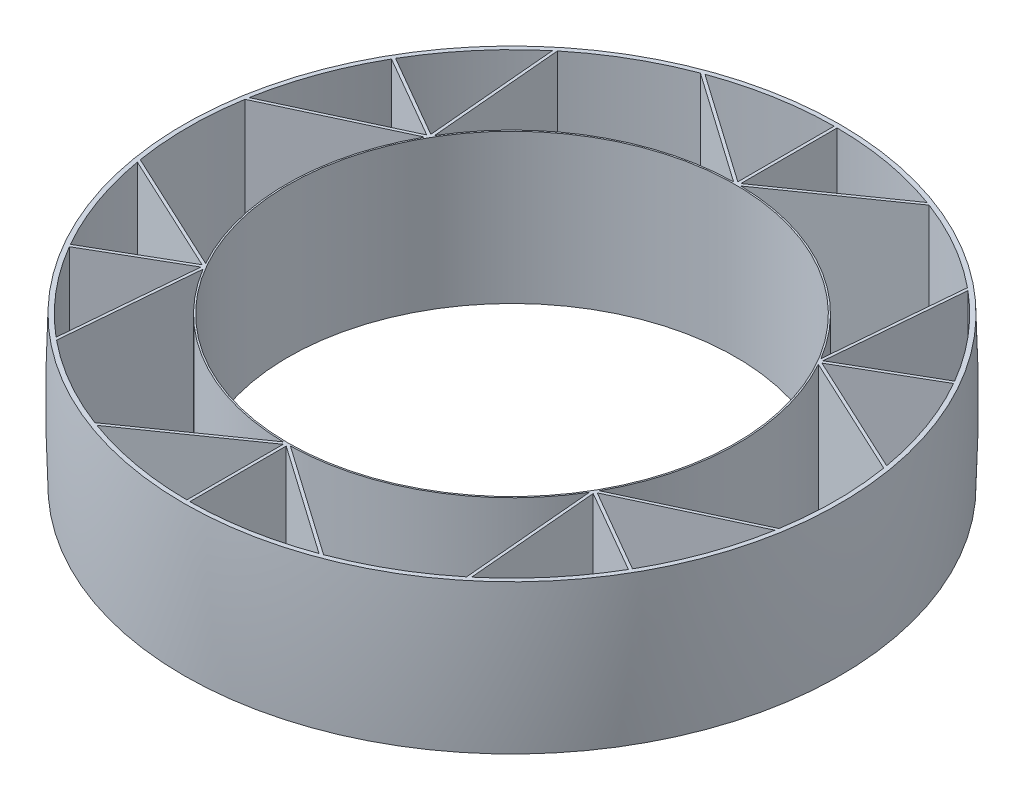
SolidWorks part; units mm, degrees
material "Бутил"
ref_plane "Спереди" through (0, 0, 0) normal (0, 0, 1) x (1, 0, 0)
ref_plane "Сверху" through (0, 0, 0) normal (0, 1, 0) x (1, 0, 0)
ref_plane "Справа" through (0, 0, 0) normal (1, 0, 0) x (0, 0, -1)
sketch "Эскиз3" plane through (0, 0, 0) normal (0, 1, 0) x (1, 0, 0)
  circle A0 centre (0, 0) radius 108.5
  circle A1 centre (0, 0) radius 110
  dimension "D1" = 220
  dimension "D2" = 217
sketch "Эскиз6" plane through (0, 0, 0) normal (0, 1, 0) x (1, 0, 0)
  circle A0 centre (0, 0) radius 75
  circle A1 centre (0, 0) radius 75.5
  dimension "D1" = 150
  dimension "D2" = 151
extrude "Бобышка-Вытянуть9" add sketch "Эскиз6" along normal blind 50 contours A1 A0 region at (-75.2865, 0, 0)
extrude "Бобышка-Вытянуть10" add sketch "Эскиз3" along normal up to surface (50 mm away) up to face at (0, 50, 75)
sketch "Эскиз7" plane through (0, 0, 0) normal (0, 1, 0) x (1, 0, 0)
  line L1 (-0.5, -75.4983) -> (-0.5, -108.4988)
  line L2 (0.5, -75.4983) -> (0.5, -108.4988)
  line L3 (0, -108.5) -> (0, 0) construction
  circle A0 centre (0, 0) radius 75.5 construction
  arc A2 (-0.5, -75.4983) -> (0.5, -75.4983) centre (0, -48.3147) ccw
  arc A3 (-0.5, -108.4988) -> (0.5, -108.4988) centre (0, 0) ccw
  circle A5 centre (0, 0) radius 108.5 construction
  point P1 (0, -75.5029)
  dimension "D4" = 27.1883
  dimension "D1" = 1
extrude "Бобышка-Вытянуть11" add sketch "Эскиз7" along normal up to surface (50 mm away) up to face at (0, 50, 75)
sketch "Эскиз4" plane through (0, 0, 0) normal (0, -1, 0) x (1, 0, 0)
  line L2 (-38.3438, 101.4988) -> (-1.2, 75.4905)
  line L4 (0.5, 108.4988) -> (0.5, 75.4983) construction
  line L6 (0, 148.9306) -> (0, 117.9564) construction
  line L7 (38.3438, 101.4988) -> (1.2, 75.4905)
  line L8 (0.5, 76.1983) -> (37.2259, 101.9141)
  line L9 (0.5, 75.4983) -> (0.5, 76.1983)
  line L10 (-0.5, 76.1983) -> (-37.2259, 101.9141)
  line L11 (-0.5, 75.4983) -> (-0.5, 76.1983)
  circle A0 centre (0, 0) radius 108.5 construction
  arc A4 (1.2, 75.4905) -> (0.5, 75.4983) centre (0, 0) ccw
  arc A5 (37.2259, 101.9141) -> (38.3438, 101.4988) centre (0, 0) cw
  circle A6 centre (0, 0) radius 75.5 construction
  arc A7 (-0.5, 108.4988) -> (0.5, 108.4988) centre (0, 0) ccw construction
  arc A8 (-37.2259, 101.9141) -> (-38.3438, 101.4988) centre (0, 0) ccw
  arc A9 (-1.2, 75.4905) -> (-0.5, 75.4983) centre (0, 0) cw
  dimension "D1" = 110
  dimension "D5" = 0.7
  dimension "D6" = 0.7
extrude "Бобышка-Вытянуть12" add sketch "Эскиз4" against normal up to surface (50 mm away) up to face at (0, 50, 75)
sketch "Эскиз5" plane through (0, 0, 0) normal (1, 0, 0) x (0, 0, -1)
  line L0 (-110, 0) -> (-110, 50)
  line L2 (-156.6734, 25) -> (-131.9727, 25) construction
  line L4 (-110, 50) -> (-110, 0)
  line L5 (-110, 25) -> (-110, 50)
  line L7 (-110, 0) -> (-110, 50)
  line L8 (0, 0) -> (0, 64.3857) construction
  arc A3 (-110, 50) -> (-110, 0) centre (489.4789, 25) ccw
  dimension "D1" = 600
revolve "Повернуть2" add sketch "Эскиз5" angle 360 about L8 region at (0, 25, 110.2084)
pattern_circular "Круговой массив9" count 6 over 360 about axis through (0, 50, 0) along (0, -1, 0) of "Бобышка-Вытянуть12" reverse direction yes
pattern_circular "Круговой массив10" count 6 over 360 about axis through (0, 50, 0) along (0, -1, 0) of "Бобышка-Вытянуть11" reverse direction yes
